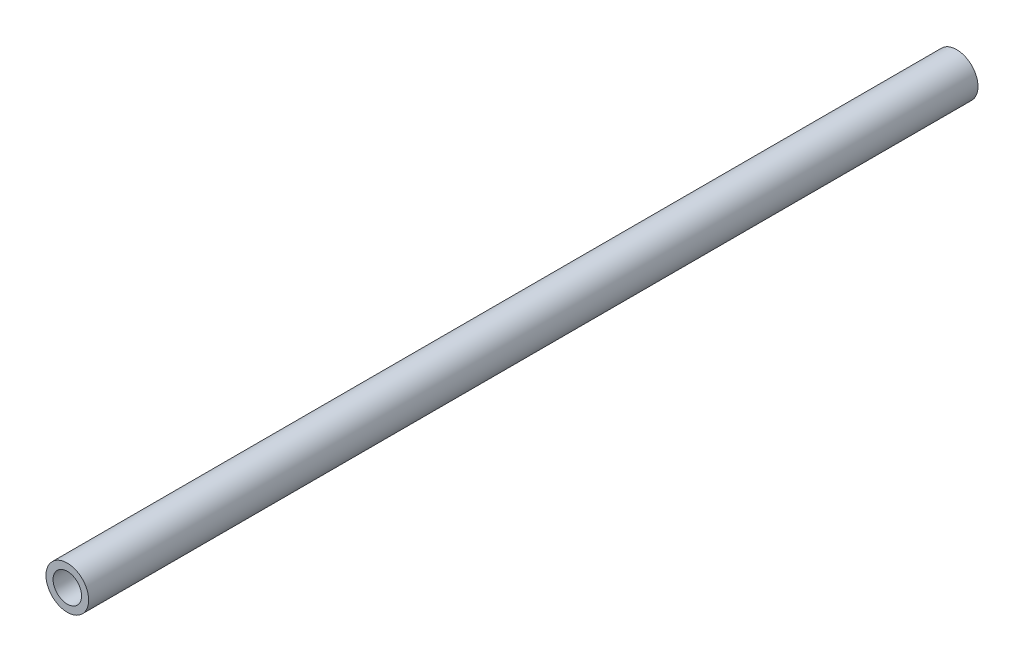
SolidWorks part; units mm, degrees
ref_plane "Front" through (0, 0, 0) normal (0, 0, 1) x (1, 0, 0)
ref_plane "Top" through (0, 0, 0) normal (0, 1, 0) x (1, 0, 0)
ref_plane "Right" through (0, 0, 0) normal (1, 0, 0) x (0, 0, -1)
sketch "Esquisse1" plane through (0, 0, 0) normal (0, 0, 1) x (1, 0, 0)
  circle A0 centre (0, 0) radius 2
  circle A1 centre (0, 0) radius 3
  dimension "D1" = 6
  dimension "D2" = 4
extrude "Boss.-Extru.1" add sketch "Esquisse1" along normal blind 125
